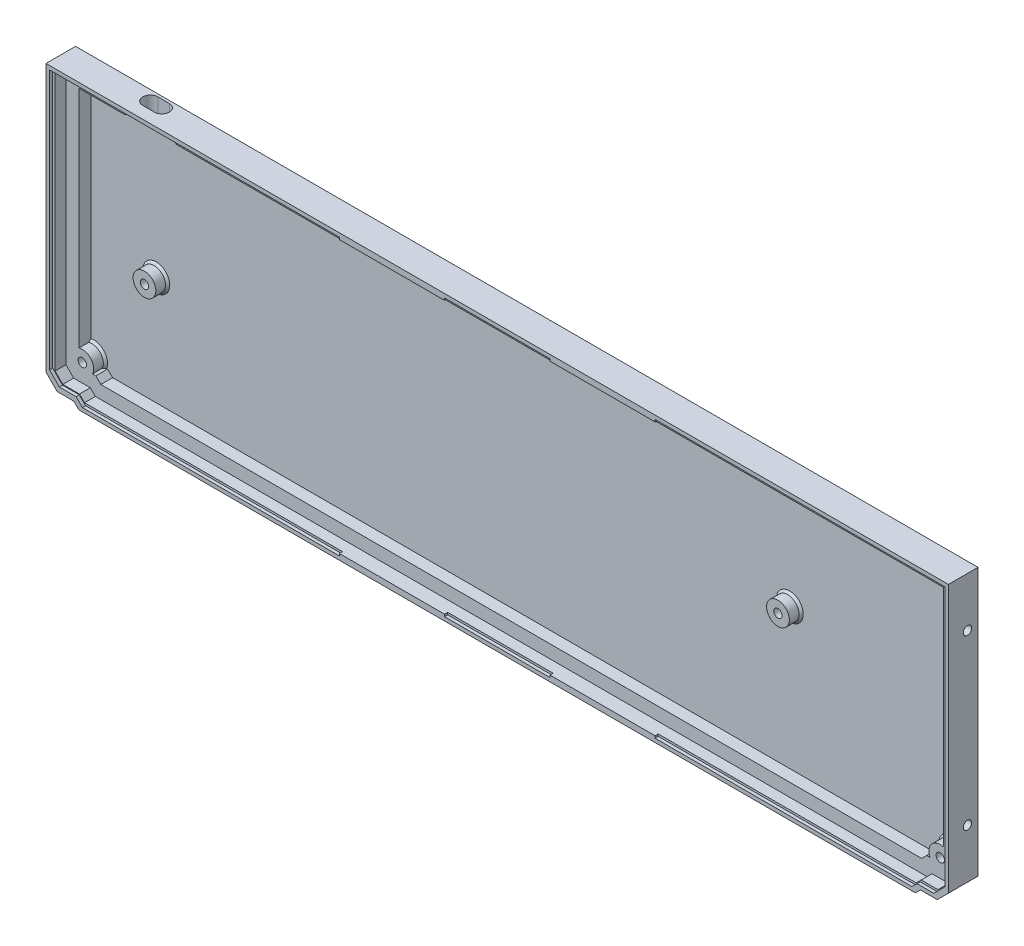
SolidWorks part; units mm, degrees
ref_plane "Přední rovina" through (0, 0, 0) normal (0, 0, 1) x (1, 0, 0)
ref_plane "Horní rovina" through (0, 0, 0) normal (0, 1, 0) x (1, 0, 0)
ref_plane "Pravá rovina" through (0, 0, 0) normal (1, 0, 0) x (0, 0, -1)
sketch "Skica3" plane through (0, 0, 0) normal (0, 0, 1) x (1, 0, 0)
  line L0 (0, 0) -> (415.1053, 0) construction
  line L1 (415.1053, 0) -> (416.6927, -1.5875) construction
  line L2 (416.6927, -1.5875) -> (416.6927, -119.8485) construction
  line L3 (0, 0) -> (-1.5875, -1.5875) construction
  line L4 (-1.5875, -1.5875) -> (-1.5875, -119.8485) construction
  line L5 (-1.5875, -119.8485) -> (0.7934, -122.2292) construction
  line L6 (0.7934, -122.2292) -> (8.7304, -122.2292) construction
  line L7 (8.7304, -122.2292) -> (11.1113, -124.61) construction
  line L8 (11.1113, -124.61) -> (403.9933, -124.61) construction
  line L9 (403.9933, -124.61) -> (406.3744, -122.2294) construction
  line L10 (406.3744, -122.2294) -> (414.3114, -122.2294) construction
  line L11 (416.6927, -119.8485) -> (414.3114, -122.2294) construction
  line L12 (2.4125, -4) -> (412.6927, -4)
  line L13 (412.6927, -4) -> (412.6927, -4)
  line L14 (412.6927, -4) -> (412.6927, -118.1914)
  line L15 (412.6927, -118.1914) -> (412.6547, -118.2294)
  line L16 (404.7177, -118.2294) -> (412.6547, -118.2294)
  line L17 (402.3367, -120.61) -> (404.7177, -118.2294)
  line L18 (12.7681, -120.61) -> (402.3367, -120.61)
  line L19 (10.3872, -118.2292) -> (12.7681, -120.61)
  line L20 (2.4502, -118.2292) -> (10.3872, -118.2292)
  line L21 (2.4125, -118.1915) -> (2.4502, -118.2292)
  line L22 (2.4125, -4) -> (2.4125, -118.1915)
  line L23 (2.4125, -4) -> (2.4125, -4)
  line L24 (-1.5875, -119.8485) -> (415.1053, 0) construction
  line L26 (0, 0) -> (416.6927, -119.8485) construction
  dimension "D1" = 135
  dimension "D2" = 135
  dimension "D3" = 4
  dimension "D4" = 2.245
  dimension "D5" = 2.245
  dimension "D6" = 118.261
  dimension "D7" = 118.261
  dimension "D8" = 3.367
  dimension "D9" = 7.937
  dimension "D10" = 3.367
  dimension "D11" = 392.882
  dimension "D12" = 3.367
  dimension "D13" = 7.937
  dimension "D14" = 3.3674
extrude "Přidat vysunutím1" add sketch "Skica3" along normal blind 5.6
shell "Skořepina1" thickness 1.8 removed face at (207.5525, -95.852, 5.6) outward yes
sketch "Skica7" plane through (0, 0, 5.6) normal (0, 0, 1) x (1, 0, 0)
  line L20 (-6.5875, 5) -> (-6.5875, -121.9196)
  line L21 (-6.5875, -121.9196) -> (-1.2775, -127.2292)
  line L22 (-1.2775, -127.2292) -> (6.6595, -127.2292)
  line L23 (6.6595, -127.2292) -> (9.0403, -129.61)
  line L24 (9.0403, -129.61) -> (406.0641, -129.61)
  line L25 (406.0641, -129.61) -> (408.4452, -127.2294)
  line L26 (408.4452, -127.2294) -> (416.3822, -127.2294)
  line L27 (416.3822, -127.2294) -> (421.6927, -121.9198)
  line L28 (421.6927, -121.9198) -> (421.6927, 5)
  line L29 (421.6927, 5) -> (-6.5875, 5)
  line L30 (-6.5875, 5) -> (-6.5875, -121.9196)
  line L31 (-6.5875, -121.9196) -> (-1.2775, -127.2292)
  line L32 (-1.2775, -127.2292) -> (6.6595, -127.2292)
  line L33 (6.6595, -127.2292) -> (9.0403, -129.61)
  line L34 (9.0403, -129.61) -> (406.0641, -129.61)
  line L35 (406.0641, -129.61) -> (408.4452, -127.2294)
  line L36 (408.4452, -127.2294) -> (416.3822, -127.2294)
  line L37 (416.3822, -127.2294) -> (421.6927, -121.9198)
  line L38 (421.6927, -121.9198) -> (421.6927, 5)
  line L39 (421.6927, 5) -> (-6.5875, 5)
  line L40 (-3.7875, 2.2) -> (-3.7875, -120.7598)
  line L41 (-3.7875, -120.7598) -> (-0.1178, -124.4292)
  line L42 (-0.1178, -124.4292) -> (7.8192, -124.4292)
  line L43 (7.8192, -124.4292) -> (10.2001, -126.81)
  line L44 (10.2001, -126.81) -> (404.9045, -126.81)
  line L45 (404.9045, -126.81) -> (407.2855, -124.4294)
  line L46 (407.2855, -124.4294) -> (415.2225, -124.4294)
  line L47 (415.2225, -124.4294) -> (418.8927, -120.7598)
  line L48 (418.8927, -120.7598) -> (418.8927, 2.2)
  line L49 (418.8927, 2.2) -> (-3.7875, 2.2)
  line L50 (-3.7875, 2.2) -> (-3.7875, -120.7598)
  line L51 (-3.7875, -120.7598) -> (-0.1178, -124.4292)
  line L52 (-0.1178, -124.4292) -> (7.8192, -124.4292)
  line L53 (7.8192, -124.4292) -> (10.2001, -126.81)
  line L54 (10.2001, -126.81) -> (404.9045, -126.81)
  line L55 (404.9045, -126.81) -> (407.2855, -124.4294)
  line L56 (407.2855, -124.4294) -> (415.2225, -124.4294)
  line L57 (415.2225, -124.4294) -> (418.8927, -120.7598)
  line L58 (418.8927, -120.7598) -> (418.8927, 2.2)
  line L59 (418.8927, 2.2) -> (-3.7875, 2.2)
  dimension "D2" = 4.4
  dimension "D1" = 7.2
extrude "Přidat vysunutím3" add sketch "Skica7" along normal blind 5.15 separate body
sketch "Skica8" plane through (0, 0, 5.6) normal (0, 0, -1) x (-1, 0, 0)
  line L0 (-421.6927, 5) -> (6.5875, 5)
  line L1 (6.5875, 5) -> (6.5875, -121.9196)
  line L2 (6.5875, 5) -> (6.5875, -121.9196) construction
  line L3 (6.5875, -121.9196) -> (1.2775, -127.2292)
  line L4 (1.2775, -127.2292) -> (-6.6595, -127.2292)
  line L5 (-6.6595, -127.2292) -> (-9.0403, -129.61)
  line L6 (-9.0403, -129.61) -> (-406.0641, -129.61)
  line L7 (-406.0641, -129.61) -> (-408.4452, -127.2294)
  line L8 (-408.4452, -127.2294) -> (-416.3822, -127.2294)
  line L9 (-416.3822, -127.2294) -> (-421.6927, -121.9198)
  line L10 (-421.6927, -121.9198) -> (-421.6927, 5)
  line L11 (-0.6125, -2.2) -> (-0.6125, -118.9371)
  line L12 (-414.4927, -2.2) -> (-0.6125, -2.2) construction
  line L13 (-0.6125, -2.2) -> (-0.6125, -118.9371) construction
  line L14 (-0.6125, -118.9371) -> (-1.7047, -120.0292)
  line L15 (-1.7047, -120.0292) -> (-9.6417, -120.0292)
  line L16 (-9.6417, -120.0292) -> (-12.0226, -122.41)
  line L17 (-12.0226, -122.41) -> (-403.0822, -122.41)
  line L18 (-403.0822, -122.41) -> (-405.4632, -120.0294)
  line L19 (-405.4632, -120.0294) -> (-413.4002, -120.0294) construction
  line L20 (-405.4632, -120.0294) -> (-413.4002, -120.0294)
  line L21 (-413.4002, -120.0294) -> (-414.4927, -118.9371) construction
  line L22 (-413.4002, -120.0294) -> (-414.4927, -118.9371)
  line L23 (-414.4927, -118.9371) -> (-414.4927, -2.2)
  line L24 (-414.4927, -2.2) -> (-0.6125, -2.2)
extrude "Přidat vysunutím4" add sketch "Skica8" along normal up to surface (7.4 mm away) up to face at (207.5525, -96.7211, -1.8)
sketch "Skica11" plane through (0, 0, 10.75) normal (0, 0, 1) x (1, 0, 0)
  line L0 (207.5526, 3.195) -> (207.5526, 5) construction
  line L1 (421.6927, 5) -> (-6.5875, 5) construction
  line L2 (207.5522, -127.805) -> (207.5522, -129.61) construction
  line L3 (9.0403, -129.61) -> (406.0641, -129.61) construction
  line L4 (-4.9474, -58.4598) -> (-6.5875, -58.4598) construction
  line L5 (-6.5875, 5) -> (-6.5875, -121.9196) construction
  line L6 (420.0526, -58.4599) -> (421.6927, -58.4599) construction
  line L7 (421.6927, -121.9198) -> (421.6927, 5) construction
  line L8 (404.9045, -126.81) -> (407.2855, -124.4294) construction
  line L9 (415.2225, -124.4294) -> (418.8927, -120.7598) construction
  line L10 (7.8192, -124.4292) -> (10.2001, -126.81) construction
  line L11 (-3.7875, -120.7598) -> (-0.1178, -124.4292) construction
  line L13 (407.2855, -124.4294) -> (415.2225, -124.4294) construction
  line L14 (-0.1178, -124.4292) -> (7.8192, -124.4292) construction
  line L30 (420.0526, 3.195) -> (-4.9474, 3.195)
  line L31 (-4.9474, 3.195) -> (-4.9474, -120.1146)
  line L32 (-4.9474, -120.1146) -> (-0.24, -124.8217)
  line L33 (-0.24, -124.8217) -> (7.697, -124.8217)
  line L34 (7.697, -124.8217) -> (10.6804, -127.805)
  line L35 (10.6804, -127.805) -> (404.4241, -127.805)
  line L36 (404.4241, -127.805) -> (406.8051, -125.4244)
  line L37 (406.8051, -125.4244) -> (414.7421, -125.4244)
  line L38 (414.7421, -125.4244) -> (420.0526, -120.1148)
  line L39 (420.0526, -120.1148) -> (420.0526, 3.195)
  line L45 (421.6927, 5) -> (-6.5875, 5)
  line L46 (-6.5875, 5) -> (-6.5875, -121.9196)
  line L47 (-6.5875, -121.9196) -> (-1.2775, -127.2292)
  line L48 (-1.2775, -127.2292) -> (6.6595, -127.2292)
  line L49 (6.6595, -127.2292) -> (9.0403, -129.61)
  line L50 (9.0403, -129.61) -> (406.0641, -129.61)
  line L51 (406.0641, -129.61) -> (408.4452, -127.2294)
  line L52 (408.4452, -127.2294) -> (416.3822, -127.2294)
  line L53 (416.3822, -127.2294) -> (421.6927, -121.9198)
  line L54 (421.6927, -121.9198) -> (421.6927, 5)
  line L55 (421.6927, 5) -> (-6.5875, 5)
  line L56 (-6.5875, 5) -> (-6.5875, -121.9196)
  line L57 (-6.5875, -121.9196) -> (-1.2775, -127.2292)
  line L58 (-1.2775, -127.2292) -> (6.6595, -127.2292)
  line L59 (6.6595, -127.2292) -> (9.0403, -129.61)
  line L60 (9.0403, -129.61) -> (406.0641, -129.61)
  line L61 (406.0641, -129.61) -> (408.4452, -127.2294)
  line L62 (408.4452, -127.2294) -> (416.3822, -127.2294)
  line L63 (416.3822, -127.2294) -> (421.6927, -121.9198)
  line L64 (421.6927, -121.9198) -> (421.6927, 5)
  point P0 (207.5523, -63.11)
  point P2 (207.5523, -63.11)
  dimension "D1" = 131
  dimension "D2" = 425
  dimension "D3" = 0
extrude "Přidat vysunutím5" add sketch "Skica11" along normal blind 1.5
sketch "Skica14" plane through (0, 0, 10.75) normal (0, 0, 1) x (1, 0, 0)
  line L0 (418.8927, 2.2) -> (-3.7875, 2.2) construction
  line L1 (182.5326, 2.2) -> (132.6326, 2.2)
  line L2 (182.5326, 2.2) -> (182.5326, 3.195)
  line L3 (182.5326, 3.195) -> (132.6326, 3.195)
  line L4 (132.6326, 2.2) -> (132.6326, 3.195)
  line L5 (420.0526, 3.195) -> (-4.9474, 3.195) construction
  line L6 (418.8927, 2.2) -> (-3.7875, 2.2) construction
  line L7 (232.5726, 2.2) -> (282.4726, 2.2)
  line L8 (232.5726, 2.2) -> (232.5726, 3.195)
  line L9 (232.5726, 3.195) -> (282.4726, 3.195)
  line L10 (282.4726, 2.2) -> (282.4726, 3.195)
  line L11 (207.5526, 3.195) -> (207.5522, -127.805) construction
  line L12 (10.6804, -127.805) -> (404.4241, -127.805) construction
  line L13 (10.2001, -126.81) -> (404.9045, -126.81) construction
  line L14 (232.5722, -126.81) -> (282.4722, -126.81)
  line L15 (232.5722, -126.81) -> (232.5722, -127.805)
  line L16 (232.5722, -127.805) -> (282.4722, -127.805)
  line L17 (282.4722, -126.81) -> (282.4722, -127.805)
  line L18 (10.6804, -127.805) -> (404.4241, -127.805) construction
  line L20 (182.5322, -126.81) -> (132.6322, -126.81)
  line L21 (182.5322, -126.81) -> (182.5322, -127.805)
  line L22 (182.5322, -127.805) -> (132.6322, -127.805)
  line L23 (132.6322, -126.81) -> (132.6322, -127.805)
  dimension "D1" = 49.9
  dimension "D2" = 49.9
  dimension "D3" = 25.02
  dimension "D4" = 25.02
  dimension "D5" = 49.9
  dimension "D6" = 49.9
  dimension "D7" = 25.02
  dimension "D8" = 25.02
extrude "Přidat vysunutím6" add sketch "Skica14" along normal up to surface (1.5 mm away) up to face at (207.5524, -100.1977, 12.25)
sketch "Skica15" plane through (0, 0, 0) normal (0, 0, 1) x (1, 0, 0)
  line L1 (34.9015, 4.5) -> (37.9015, 4.5)
  line L2 (34.9015, 4.5) -> (34.9015, -4.5)
  line L3 (34.9015, -4.5) -> (37.9015, -4.5)
  line L4 (37.9015, 4.5) -> (37.9015, -4.5)
  line L5 (34.9015, 4.5) -> (37.9015, -4.5) construction
  line L6 (34.9015, -4.5) -> (37.9015, 4.5) construction
  line L20 (-1.5875, 0) -> (-1.5875, -119.8485)
  line L21 (-1.5875, -119.8485) -> (0.7934, -122.2292)
  line L22 (0.7934, -122.2292) -> (8.7304, -122.2292)
  line L23 (8.7304, -122.2292) -> (11.1113, -124.61)
  line L24 (11.1113, -124.61) -> (403.9933, -124.61)
  line L25 (403.9933, -124.61) -> (406.3744, -122.2294)
  line L26 (406.3744, -122.2294) -> (414.3114, -122.2294)
  line L27 (414.3114, -122.2294) -> (416.6927, -119.8485)
  line L28 (416.6927, -119.8485) -> (416.6927, 0)
  line L29 (416.6927, 0) -> (-1.5875, 0)
  line L30 (-1.5875, 0) -> (-1.5875, -119.8485) construction
  line L31 (-1.5875, -119.8485) -> (0.7934, -122.2292) construction
  line L32 (0.7934, -122.2292) -> (8.7304, -122.2292) construction
  line L33 (8.7304, -122.2292) -> (11.1113, -124.61) construction
  line L34 (11.1113, -124.61) -> (403.9933, -124.61) construction
  line L35 (403.9933, -124.61) -> (406.3744, -122.2294) construction
  line L36 (406.3744, -122.2294) -> (414.3114, -122.2294) construction
  line L37 (414.3114, -122.2294) -> (416.6927, -119.8485) construction
  line L38 (416.6927, -119.8485) -> (416.6927, 0) construction
  line L39 (416.6927, 0) -> (-1.5875, 0) construction
  circle A0 centre (3.9685, -115.9542) radius 5.4
  circle A1 centre (33.4915, -69.051) radius 5.4
  circle A2 centre (411.1977, -115.8794) radius 5.4
  circle A3 centre (334.1477, -53.972) radius 5.4
  point P2 (-1.4315, -115.9542)
  point P3 (3.9685, -121.3542)
  point P4 (28.0915, -69.051)
  point P8 (33.4915, -74.451)
  point P12 (411.1977, -121.2794)
  point P13 (416.5977, -115.8794)
  point P17 (334.1477, -48.572)
  point P19 (339.5477, -53.972)
  point P21 (36.4015, 0)
  point P23 (36.4015, 0)
  dimension "D2" = 0.156
  dimension "D4" = 10.8
  dimension "D7" = 10.8
  dimension "D10" = 10.8
  dimension "D13" = 10.8
  dimension "D3" = 0.875
  dimension "D5" = 29.679
  dimension "D6" = 50.159
  dimension "D8" = 0.095
  dimension "D9" = 0.95
  dimension "D11" = 77.145
  dimension "D12" = 48.572
  dimension "D14" = 37.989
  dimension "D15" = 9
  dimension "D16" = 3
  dimension "D1" = 4
extrude "Přidat vysunutím7" add sketch "Skica15" along normal blind 5.6
sketch "Skica16" plane through (0, 0, 5.6) normal (0, 0, 1) x (1, 0, 0)
  circle A0 centre (3.9685, -115.9542) radius 2
  circle A1 centre (33.4915, -69.051) radius 2
  circle A2 centre (334.1477, -53.972) radius 2
  circle A3 centre (411.1977, -115.8794) radius 2
  dimension "D1" = 4
  dimension "D2" = 4
  dimension "D3" = 4
  dimension "D4" = 4
extrude "Odebrat vysunutím1" cut sketch "Skica16" against normal blind 5.75
chamfer "Zkosení1" distance 1 angle 45 4 edges at (407.0694, -112.3984, 0) (8.0492, -112.4175, 0) (38.8915, -69.051, 0) (339.5477, -53.972, 0)
sketch "Skica17" plane through (0, 0, 5.6) normal (0, 0, 1) x (1, 0, 0)
  line L0 (34.9015, -4.5) -> (37.9015, -4.5) construction
  line L1 (24.4015, -11.2) -> (48.4015, -11.2)
  line L2 (24.4015, -11.2) -> (24.4015, 2.2)
  line L3 (24.4015, 2.2) -> (48.4015, 2.2)
  line L4 (48.4015, -11.2) -> (48.4015, 2.2)
  line L5 (24.4015, -11.2) -> (48.4015, 2.2) construction
  line L6 (24.4015, 2.2) -> (48.4015, -11.2) construction
  line L7 (418.8927, 2.2) -> (-3.7875, 2.2) construction
  point P0 (36.4015, -4.5)
  dimension "D1" = 24
extrude "Odebrat vysunutím2" cut sketch "Skica17" against normal blind 1.6
sketch "Skica18" plane through (0, -4.5, 0) normal (0, -1, 0) x (1, 0, 0)
  line L0 (33.6515, 3) -> (39.1515, 3) construction
  line L3 (33.6515, 6.55) -> (39.1515, 6.55)
  line L4 (33.6515, -0.55) -> (39.1515, -0.55)
  line L5 (36.4015, 4) -> (36.4015, 3) construction
  line L6 (37.9015, 4) -> (34.9015, 4) construction
  arc A0 (33.6515, 6.55) -> (33.6515, -0.55) centre (33.6515, 3) ccw
  arc A1 (39.1515, -0.55) -> (39.1515, 6.55) centre (39.1515, 3) ccw
  point P6 (36.4015, 3)
  point P11 (30.1015, 3)
  point P12 (42.7015, 3)
  dimension "D1" = 12.6
  dimension "D2" = 7.1
  dimension "D3" = 1
extrude "Odebrat vysunutím3" cut sketch "Skica18" against normal up to surface (9.5 mm away) up to face at (207.5526, 5, 5.225)
sketch "Skica23" plane through (-6.5875, 0, 0) normal (-1, 0, 0) x (0, 0, 1)
  line L2 (-1.8, 5) -> (-1.8, -121.9196) construction
  line L4 (-1.8, -58.4598) -> (12.25, -58.4598) construction
  line L5 (12.25, 5) -> (12.25, -121.9196) construction
  circle A0 centre (3.2, -18.4598) radius 2
  circle A1 centre (3.2, -98.4598) radius 2
  point P8 (-1.8, -58.4598)
  dimension "D2" = 4
  dimension "D3" = 4
  dimension "D1" = 40
  dimension "D4" = 5
extrude "Odebrat vysunutím4" cut sketch "Skica23" against normal blind 5.7
sketch "Skica24" plane through (421.6927, 0, 0) normal (1, 0, 0) x (0, 0, -1)
  line L0 (1.8, -58.4599) -> (-12.25, -58.4599) construction
  line L1 (1.8, -121.9198) -> (1.8, 5) construction
  line L2 (-12.25, -121.9198) -> (-12.25, 5) construction
  circle A0 centre (-3.2, -18.4599) radius 2
  circle A1 centre (-3.2, -98.4599) radius 2
  dimension "D1" = 4
  dimension "D2" = 4
  dimension "D3" = 40
  dimension "D4" = 5
extrude "Odebrat vysunutím5" cut sketch "Skica24" against normal blind 5.7
sketch "Skica25" plane through (0, 0, -1.8) normal (0, 0, -1) x (-1, 0, 0)
  line L0 (-421.6927, -121.9198) -> (-421.6927, 5) construction
  line L1 (-421.6927, 5) -> (6.5875, 5) construction
  line L2 (6.5875, 5) -> (6.5875, -121.9196) construction
  line L3 (-9.0403, -129.61) -> (-406.0641, -129.61) construction
  circle A0 centre (-401.6927, -15) radius 6.25
  circle A1 centre (-13.4125, -15) radius 6.25
  circle A2 centre (-388.4452, -109.61) radius 6.25
  circle A3 centre (-26.6595, -109.61) radius 6.25
  dimension "D1" = 12.5
  dimension "D2" = 12.5
  dimension "D3" = 12.5
  dimension "D4" = 12.5
  dimension "D5" = 20
  dimension "D6" = 20
  dimension "D7" = 20
  dimension "D8" = 20
  dimension "D9" = 20
  dimension "D10" = 20
  dimension "D11" = 20
  dimension "D12" = 20
extrude "Odebrat vysunutím6" cut sketch "Skica25" against normal blind 1.5
